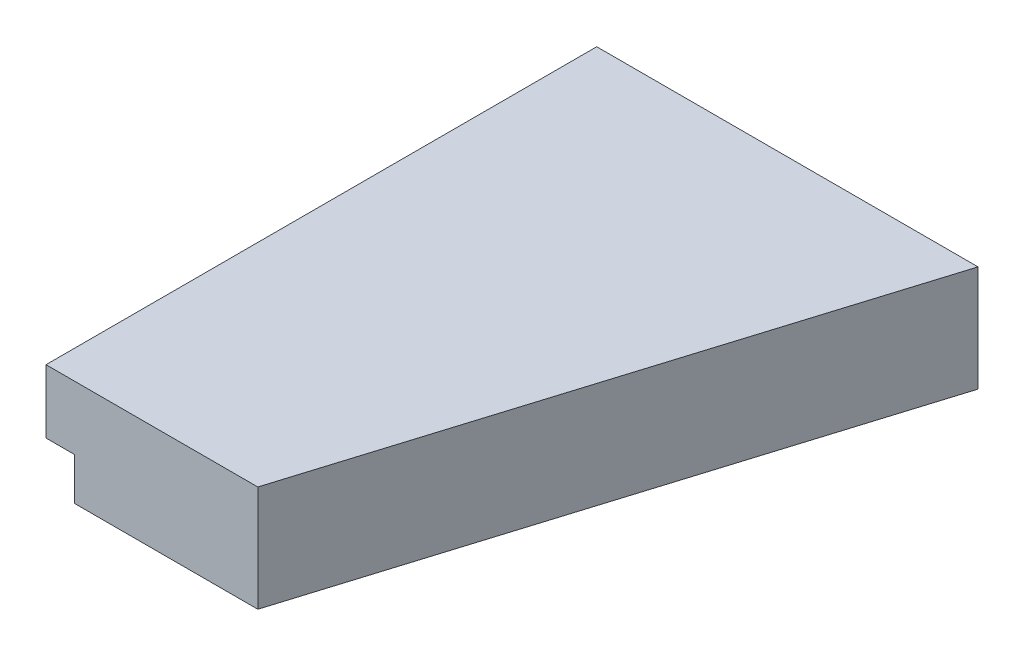
SolidWorks part; units mm, degrees
ref_plane "Front Plane" through (0, 0, 0) normal (1, 0, 0) x (0, 1, 0)
ref_plane "Top Plane" through (0, 0, 0) normal (0, 0, 1) x (0, 1, 0)
ref_plane "Right Plane" through (0, 0, 0) normal (0, 1, 0) x (-1, 0, 0)
sketch "Sketch1" plane through (0, 0, 0) normal (0, 1, 0) x (-1, 0, 0)
  line L0 (-13.4363, 17.5951) -> (26.5637, 147.5951)
  line L1 (-13.4363, 10.0951) -> (-8.4363, 10.0951)
  line L2 (-13.4363, 10.0951) -> (-13.4363, 17.5951)
  line L3 (-13.4363, 17.5951) -> (-8.4363, 17.5951)
  line L4 (-8.4363, 10.0951) -> (-8.4363, 17.5951)
  line L13 (-13.4363, 17.5951) -> (26.5637, 147.5951)
  line L14 (-13.4363, 17.5951) -> (-3.8786, 14.6542)
  line L15 (-13.4363, 17.5951) -> (66.5637, 17.5951) construction
  line L16 (-13.4363, 17.5951) -> (-13.4363, 137.5951) construction
  line L17 (-13.4363, 137.5951) -> (66.5637, 137.5951) construction
  line L18 (66.5637, 17.5951) -> (66.5637, 137.5951) construction
  line L19 (66.5637, 137.5951) -> (26.5637, 137.5951)
  line L20 (66.5637, 137.5951) -> (66.5637, 147.5951)
  line L21 (66.5637, 147.5951) -> (26.5637, 147.5951)
  line L22 (26.5637, 137.5951) -> (26.5637, 147.5951)
  line L23 (26.5637, 147.5951) -> (36.1214, 144.6542)
  line L24 (-3.8786, 14.6542) -> (36.1214, 144.6542)
  line L25 (-8.4363, 17.5951) -> (-2.9737, 17.5951)
  line L27 (-2.9737, 17.5951) -> (66.5637, 17.5951)
  line L28 (-2.9737, 17.5951) -> (-2.9737, 22.5951)
  line L29 (-2.9737, 22.5951) -> (66.5637, 22.5951)
  line L30 (66.5637, 17.5951) -> (66.5637, 22.5951)
  line L35 (66.5637, 147.5951) -> (76.5637, 147.5951)
  line L36 (66.5637, 147.5951) -> (66.5637, 17.5951)
  line L37 (66.5637, 17.5951) -> (76.5637, 17.5951)
  line L38 (76.5637, 147.5951) -> (76.5637, 17.5951)
  point P17 (66.5637, 17.5951)
  dimension "D1" = 7.5
  dimension "D2" = 5
  dimension "D3" = 120
  dimension "D4" = 80
  dimension "D5" = 10
  dimension "D6" = 40
  dimension "D7" = 10
  dimension "D9" = 5
  dimension "D8" = 10
extrude "Boss-Extrude1" add sketch "Sketch1" along normal blind 25 contours L24 L19 L20 L21 L23 | L19 L24 L23 L22 | L3 L25 L24 L19 L22 L0 | L29 L28 L24 | L27 L30 L29 L24 | L38 L35 L20 L36 L30 L37 region at (-10.4807, 0, 78.5361) region at (-30.6185, 0, 142.1049) region at (-50.1746, 0, 142.7061) region at (-71.5637, 0, 82.5951) region at (2.4609, 0, 20.9284) region at (-32.1782, 0, 20.0858)
sketch "Sketch2" plane through (0, 25, 0) normal (0, 1, 0) x (-1, 0, 0)
  line L0 (26.5637, 147.5951) -> (76.5637, 147.5951)
  line L1 (76.5637, 147.5951) -> (76.5637, 17.5951)
  line L2 (76.5637, 17.5951) -> (-13.4363, 17.5951)
  line L3 (-13.4363, 17.5951) -> (26.5637, 147.5951)
  line L5 (-13.4363, 17.5951) -> (76.5637, 17.5951) construction
  point P4 (66.5637, 17.5951)
  point P9 (66.5637, 17.5951)
  point P12 (76.5637, 147.5951)
  point P14 (76.5637, 17.5951)
extrude "Boss-Extrude2" add sketch "Sketch2" against normal blind 10
sketch "Sketch3" plane through (0, 0, 0) normal (0, -1, 0) x (1, 0, 0)
  line L1 (-33.9494, 147.5951) -> (-66.5637, 147.5951)
  line L2 (-33.9494, 147.5951) -> (-33.9494, 137.5951)
  line L3 (-33.9494, 137.5951) -> (-66.5637, 137.5951)
  line L4 (-66.5637, 147.5951) -> (-66.5637, 137.5951)
  line L17 (-76.5637, 147.5951) -> (-26.5637, 147.5951) construction
  line L22 (1.4352, 22.5951) -> (-33.9494, 137.5951)
  line L23 (1.4352, 22.5951) -> (10.993, 25.5359)
  line L24 (-33.9494, 137.5951) -> (-24.3916, 140.5359)
  line L26 (10.993, 25.5359) -> (-24.3916, 140.5359)
  line L27 (13.4363, 17.5951) -> (-26.5637, 147.5951) construction
  line L28 (-37.1994, 140.8451) -> (-63.3137, 140.8451)
  line L29 (-63.3137, 144.3451) -> (-63.3137, 140.8451)
  line L30 (-37.1994, 144.3451) -> (-63.3137, 144.3451)
  line L31 (-37.1994, 144.3451) -> (-37.1994, 140.8451)
  line L32 (-29.8873, 135.4446) -> (-26.5421, 136.4739)
  line L33 (6.9309, 27.6864) -> (-26.5421, 136.4739)
  line L34 (3.5857, 26.6571) -> (6.9309, 27.6864)
  line L35 (3.5857, 26.6571) -> (-29.8873, 135.4446)
  line L36 (-26.5421, 136.4739) -> (-29.8873, 135.4446)
  line L37 (-29.8873, 135.4446) -> (-33.626, 147.5951)
  line L38 (-26.5421, 136.4739) -> (-29.964, 147.5951)
  line L39 (-37.1994, 140.8451) -> (-27.8871, 140.8451)
  line L40 (-37.1994, 144.3451) -> (-28.964, 144.3451)
  line L41 (-28.964, 144.3451) -> (-27.8871, 140.8451)
  dimension "D1" = 3.25
extrude "Cut-Extrude1" cut sketch "Sketch3" against normal blind 10 contours L31 L30 L29 L28 | L35 L34 L33 L32 region at (-50.2565, 0, 142.5951) region at (-11.4782, 0, 81.5655)
sketch "Sketch4" plane through (0, 0, 22.5951) normal (0, 1, 0) x (1, 0, 0)
  line L5 (13.4363, 5) -> (-76.5637, 5) construction
  line L6 (-66.5637, 0) -> (1.4352, 0)
  line L7 (-66.5637, 0) -> (-66.5637, 5)
  line L8 (-66.5637, 5) -> (1.4352, 5)
  line L9 (1.4352, 0) -> (1.4352, 5)
  line L10 (1.4352, 0) -> (2.9737, 5)
  line L11 (1.4352, 0) -> (-33.9494, -115) construction
  line L12 (2.9737, 5) -> (1.4352, 5)
  line M13 (1.4352, 0) -> (-66.5637, 0)
  line M20 (-76.5637, 5) -> (13.4363, 5)
extrude "Cut-Extrude2" cut sketch "Sketch4" along normal blind 0.625 contours L9 L7 M13 M20 | L10 L9 M20 region at (-32.5642, 0, 20.0951) region at (1.948, 0, 19.2617)
sketch "Sketch5" plane through (0, 0, 22.5951) normal (0, 0, 1) x (1, 0, 0)
  line L1 (-66.5637, 0.625) -> (-59.3137, 0.625) construction
  line L2 (-66.5637, 0.625) -> (-66.5637, 5.625) construction
  line L3 (-66.5637, 5.625) -> (-59.3137, 5.625) construction
  line L4 (-59.3137, 0.625) -> (-59.3137, 5.625) construction
  circle A0 centre (-59.3137, 5.625) radius 1.9
  point P6 (-66.5637, 0.625)
  dimension "D3" = 3.8
  dimension "D1" = 5
  dimension "D2" = 7.25
extrude "Cut-Extrude3" cut sketch "Sketch5" against normal up to next contours A0
sketch "Sketch6" plane through (0, 0, 22.5951) normal (0, 0, 1) x (1, 0, 0)
  circle A0 centre (-59.3137, 5.625) radius 3.35
  dimension "D1" = 6.7
extrude "Cut-Extrude4" cut sketch "Sketch6" against normal blind 2.5
pattern_linear "LPattern1" count 2 spacing 52.5 along (1, 0, 0) of "Cut-Extrude4", "Cut-Extrude3"
sketch "Sketch7" plane through (0, 0, 0) normal (0, -1, 0) x (1, 0, 0)
  line L0 (-66.5637, 17.5951) -> (-76.5637, 17.5951) construction
  line L1 (-76.5637, 147.5951) -> (-73.3137, 147.5951)
  line L2 (-76.5637, 147.5951) -> (-76.5637, 17.5951)
  line L3 (-76.5637, 17.5951) -> (-73.3137, 17.5951)
  line L4 (-73.3137, 147.5951) -> (-73.3137, 17.5951) construction
  line L5 (-76.5637, 147.5951) -> (-26.5637, 147.5951) construction
  line L6 (-66.5637, 17.5951) -> (-69.8137, 17.5951)
  line L7 (-66.5637, 17.5951) -> (-66.5637, 147.5951)
  line L8 (-66.5637, 147.5951) -> (-69.8137, 147.5951)
  line L9 (-69.8137, 17.5951) -> (-69.8137, 147.5951) construction
  line L11 (-69.8137, 17.5951) -> (-73.3137, 17.5951)
  line L12 (-69.8137, 17.5951) -> (-69.8137, 147.5951)
  line L13 (-69.8137, 147.5951) -> (-73.3137, 147.5951)
  line L14 (-73.3137, 17.5951) -> (-73.3137, 147.5951)
  line M13 (-76.5637, 17.5951) -> (-66.5637, 17.5951)
  line M20 (-26.5637, 147.5951) -> (-76.5637, 147.5951)
  line M21 (-76.5637, 147.5951) -> (-76.5637, 17.5951)
  dimension "D1" = 3.25
  dimension "D2" = 3.25
extrude "Cut-Extrude5" cut sketch "Sketch7" against normal blind 10 contours L14 L12 M13 M20 | L14 M13 M20 M21 region at (-74.9387, 0, 82.5951) region at (-71.5637, 0, 82.5951)
equation "\"whitekey_cutout_length\"= 101.5"
equation "\"key_mount_recess_length\"=50"
equation "\"key_mount_recess_height\"=12.5"
equation "\"key_mount_recess_depth\"=1.5"
equation "\"wall_thickness\"=10"
equation "\"guide_brace_height\"=20"
equation "\"guide_brace_thickness\"=2"
equation "\"dowel_recess_depth\"=10"
equation "\"dowel_recess_offset\"=3.25"
equation "\"dowel_insert_tolerance\"=0.1"
equation "\"base_mount_height\"=40"
equation "\"base_rear_length\"=80"
equation "\"base_front_length\"=111.5"
equation "\"screw_hole_wall_offset\"=7.25"
equation "\"screw_hole_edge_inset\"=\"dowel_recess_depth\"/2"
equation "\"screw_hole_diameter\"=3.8"
equation "\"screw_head_hole_diameter\"=6.7"
equation "\"screw_nut_hole_side_len\"=3.5"
equation "\"screw_nut_recess_offset\"=0.35"
equation "\"screw_head_and_nut_recess_depth\"=2.5"
equation "\"screw_shaft_diameter\"=3.5"
equation "\"switch_board_width\"=30"
equation "\"switch_board_thickness\"=1.6"
equation "\"switch_board_wall_offset\"=11.5"
equation "\"heatset_insert_hole_diameter\"=4.8"
equation "\"heatset_insert_hole_depth\"=3.8"
equation "\"front_rear_panel_width\"=23.75"
equation "\"front_panel_height\"=24"
equation "\"front_rear_panel_recess_depth\"=5"
equation "\"rod_diameter\"=5"
equation "\"rod_head_diameter\"=8"
equation "\"rod_length_adj\"=0.5"
equation "\"rod_insert_length\"=2.8"
equation "\"switch_black_key_mount_height\"=8"
equation "\"switch_white_key_mount_height\"=3"
equation "\"D5@Sketch1\"=\"wall_thickness\""
equation "\"D7@Sketch1\"=\"wall_thickness\""
equation "\"D2@Sketch1\"=\"wall_thickness\"/2"
equation "\"D4@Sketch1\"=\"base_rear_length\""
equation "\"D3@Sketch1\"=\"base_mount_height\"*3"
equation "\"D1@Sketch1\"=\"wall_thickness\"*0.75"
equation "\"whitekey_spacing\"=1.25"
equation "\"D1@Boss-Extrude1\"=\"side_panel_depth\""
equation "\"D9@Sketch1\"=\"wall_thickness\"/2"
equation "\"D1@Boss-Extrude2\"=\"wall_thickness\""
equation "\"D8@Sketch1\"=\"wall_thickness\""
equation "\"D1@Sketch3\"=\"dowel_recess_offset\""
equation "\"D1@Cut-Extrude1\"=\"dowel_recess_depth\""
equation "\"side_panel_depth\"=25"
equation "\"D1@Sketch5\"=\"screw_hole_edge_inset\""
equation "\"D2@Sketch5\"=\"screw_hole_wall_offset\""
equation "\"D3@Sketch5\"=\"screw_hole_diameter\""
equation "\"D1@Sketch6\"=\"screw_head_hole_diameter\""
equation "\"D1@Cut-Extrude4\"=\"screw_head_and_nut_recess_depth\""
equation "\"D3@LPattern1\"=\"base_rear_length\"-\"screw_hole_wall_offset\"*2-\"wall_thickness\"-3"
equation "\"D1@Sketch7\"=\"dowel_recess_offset\""
equation "\"D2@Sketch7\"=\"dowel_recess_offset\""
equation "\"D1@Cut-Extrude5\"=\"front_rear_panel_recess_depth\"*2"
equation "\"D1@Cut-Extrude2\"=\"whitekey_spacing\"/2"
